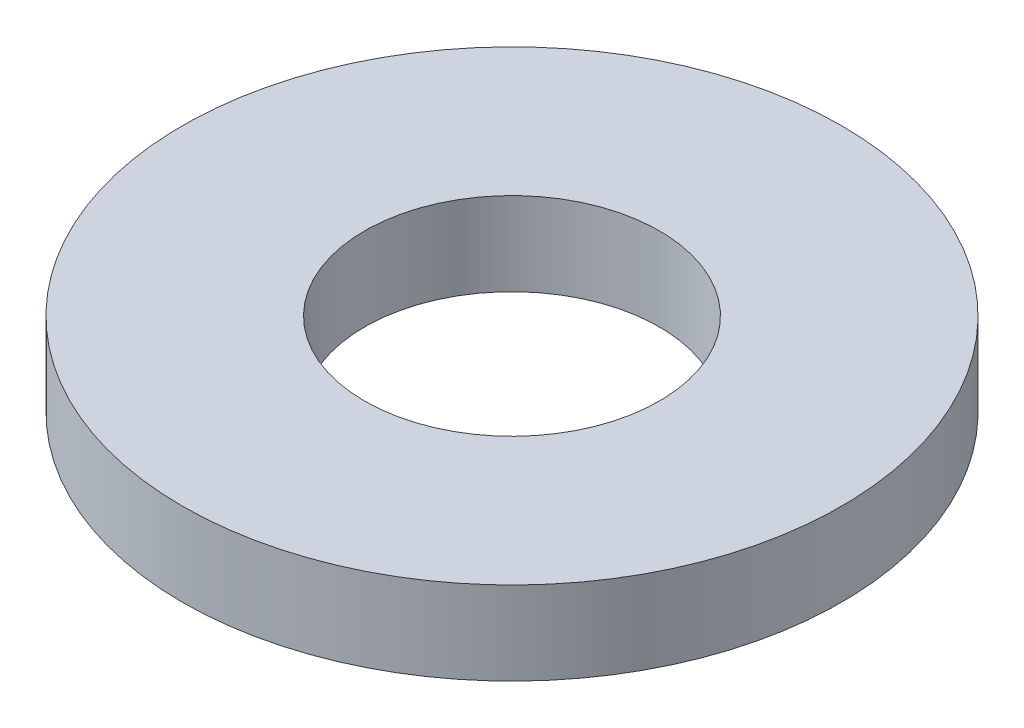
SolidWorks part; units mm, degrees
ref_plane "Front Plane" through (0, 0, 0) normal (0, 0, 1) x (1, 0, 0)
ref_plane "Top Plane" through (0, 0, 0) normal (0, 1, 0) x (1, 0, 0)
ref_plane "Right Plane" through (0, 0, 0) normal (1, 0, 0) x (0, 0, -1)
sketch "Sketch1" plane through (0, 0, 0) normal (0, 1, 0) x (1, 0, 0)
  circle A0 centre (0, 0) radius 95
  dimension "FLANGE_OD" = 190
extrude "Boss-Extrude1" add sketch "Sketch1" along normal blind 24
sketch "Sketch2" plane through (0, 0, 0) normal (0, 1, 0) x (1, 0, 0)
  circle A0 centre (0, 0) radius 42.5
  dimension "BORE_D" = 85
extrude "Cut-Extrude1" cut sketch "Sketch2" along normal through all
sketch "Sketch3" plane through (0, 24, 0) normal (0, 1, 0) x (1, 0, 0)
  circle A0 centre (0, 0) radius 27.6015 construction
  circle A1 centre (-27.6015, 0) radius 3.1074
  dimension "BOLT_D" = 6.2147
  dimension "BOLT_PCD" = 55.203
extrude "Cut-Extrude2" cut sketch "Sketch3" against normal blind 16.6662 rebuild error yes
pattern_circular "CirPattern1" count 6 over 360 rebuild error yes
